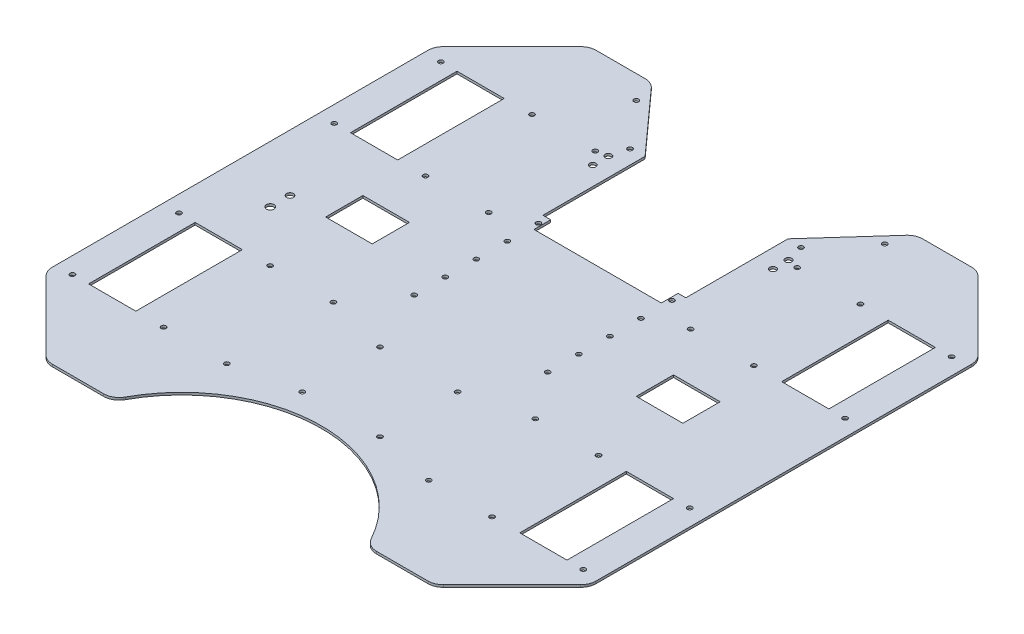
SolidWorks part; units mm, degrees
material "PMMA"
ref_plane "前视基准面" through (0, 0, 0) normal (0, 0, 1) x (1, 0, 0)
ref_plane "上视基准面" through (0, 0, 0) normal (0, 1, 0) x (1, 0, 0)
ref_plane "右视基准面" through (0, 0, 0) normal (1, 0, 0) x (0, 0, -1)
other "Configuration Table"
sketch "草图1" plane through (0, 0, 0) normal (0, 1, 0) x (1, 0, 0)
  line L0 (-125, 175) -> (-175, 125)
  line L1 (125, -175) -> (81.7103, -175)
  line L2 (175, -125) -> (175, 125)
  line L3 (125, 175) -> (85, 175)
  line L4 (-175, -125) -> (-175, 125)
  line L5 (-85, 175) -> (-40, 125)
  line L7 (125, 175) -> (175, 125)
  line L8 (175, -125) -> (125, -175)
  line L9 (-125, -175) -> (-175, -125)
  line L10 (40, 125) -> (85, 175)
  line L11 (-85, 175) -> (-125, 175)
  line L12 (40, 125) -> (40, 85)
  line L13 (40, 85) -> (-40, 85)
  line L14 (-40, 85) -> (-40, 125)
  line L15 (-153.994, 50) -> (-123.594, 50)
  line L16 (-123.594, 50) -> (-123.594, 118.58)
  line L17 (-123.594, 118.58) -> (-153.994, 118.58)
  line L18 (-153.994, 118.58) -> (-153.994, 50)
  line L19 (123.594, 50) -> (153.994, 50)
  line L20 (153.994, 50) -> (153.994, 118.58)
  line L21 (153.994, 118.58) -> (123.594, 118.58)
  line L22 (123.594, 118.58) -> (123.594, 50)
  line L23 (-175, 0) -> (175, 0) construction
  line L24 (-123.594, -118.58) -> (-153.994, -118.58)
  line L25 (-123.594, -50) -> (-123.594, -118.58)
  line L26 (-153.994, -50) -> (-123.594, -50)
  line L27 (-153.994, -118.58) -> (-153.994, -50)
  line L28 (153.994, -118.58) -> (123.594, -118.58)
  line L29 (153.994, -50) -> (153.994, -118.58)
  line L30 (123.594, -50) -> (153.994, -50)
  line L31 (123.594, -118.58) -> (123.594, -50)
  line L32 (-81.7103, -175) -> (-125, -175)
  line L33 (-80, 160) -> (-55, 131) construction
  line L34 (0, 85) -> (0, -124.4881) construction
  line L35 (-40, 85) -> (-40, -25)
  line L36 (-40, -25) -> (40, -25)
  line L37 (40, -25) -> (40, 85)
  line L38 (-40, -25) -> (-40, 66.9577)
  line L39 (-40, 66.9577) -> (40, 66.9577)
  line L40 (40, 66.9577) -> (40, -25)
  circle A0 centre (-55, 131) radius 1.55
  circle A1 centre (-80, 160) radius 1.55
  circle A2 centre (55, 131) radius 1.55
  circle A3 centre (80, 160) radius 1.55
  circle A4 centre (-65, 118.58) radius 1.55
  circle A5 centre (-65, 50) radius 1.55
  circle A6 centre (-105.72, 50) radius 1.55
  circle A7 centre (-105.72, 118.58) radius 1.55
  circle A12 centre (-164.434, 118.58) radius 1.55
  circle A13 centre (-164.434, 50) radius 1.55
  circle A14 centre (-65, -118.58) radius 1.55
  circle A15 centre (-65, -50) radius 1.55
  circle A16 centre (-105.72, -50) radius 1.55
  circle A17 centre (-105.72, -118.58) radius 1.55
  circle A18 centre (-164.434, -50) radius 1.55
  circle A19 centre (-164.434, -118.58) radius 1.55
  circle A20 centre (65, 50) radius 1.55
  circle A21 centre (105.72, 50) radius 1.55
  circle A22 centre (105.72, 118.58) radius 1.55
  circle A23 centre (65, 118.58) radius 1.55
  circle A24 centre (164.434, 118.58) radius 1.55
  circle A25 centre (164.434, 50) radius 1.55
  circle A26 centre (164.434, -118.58) radius 1.55
  circle A27 centre (164.434, -50) radius 1.55
  circle A28 centre (105.72, -50) radius 1.55
  circle A29 centre (105.72, -118.58) radius 1.55
  circle A30 centre (65, -118.58) radius 1.55
  circle A31 centre (65, -50) radius 1.55
  arc A32 (-81.7103, -175) -> (81.7103, -175) centre (0, -212.7283) cw
  circle A33 centre (25, -60) radius 1.55
  circle A34 centre (25, -110) radius 1.55
  circle A35 centre (-25, -60) radius 1.55
  circle A36 centre (-25, -110) radius 1.55
  circle A37 centre (-43, 120) radius 2.05
  circle A38 centre (-43, 110) radius 2.05
  circle A39 centre (-58, 110) radius 2.05
  circle A40 centre (-58, 120) radius 2.05
  circle A41 centre (43, 120) radius 2.05
  circle A42 centre (58, 120) radius 2.05
  circle A43 centre (58, 110) radius 2.05
  circle A44 centre (43, 110) radius 2.05
  circle A45 centre (43, -20) radius 1.55
  circle A46 centre (43, 0) radius 1.55
  circle A47 centre (43, 20) radius 1.55
  circle A48 centre (43, 40) radius 1.55
  circle A49 centre (43, 60) radius 1.55
  circle A50 centre (-43, -20) radius 1.55
  circle A51 centre (-43, 0) radius 1.55
  circle A52 centre (-43, 20) radius 1.55
  circle A53 centre (-43, 40) radius 1.55
  circle A54 centre (-43, 60) radius 1.55
  circle A55 centre (-138.4729, -4.4575) radius 2.205
  circle A56 centre (-138.4729, -17.1575) radius 2.5
  point P0 (0, 0)
  point P1 (-85, 175)
  point P2 (85, 175)
  point P3 (40, 125)
  point P4 (-40, 125)
  point P6 (125, 175)
  point P8 (175, 125)
  point P10 (175, -125)
  point P11 (125, -175)
  point P12 (-125, -175)
  point P13 (-175, -125)
  point P24 (-80, 160)
  point P25 (-55, 131)
  point P26 (55, 131)
  point P27 (80, 160)
  point P36 (-164.434, 118.58)
  point P37 (-164.434, 50)
  point P38 (-153.994, 118.58)
  point P39 (-123.594, 50)
  point P40 (-105.72, 118.58)
  point P41 (-105.72, 50)
  point P42 (-65, 118.58)
  point P43 (-65, 50)
  point P47 (-123.594, 118.58)
  point P53 (-153.994, 50)
  point P66 (-40, 85)
  point P67 (40, 85)
  point P70 (105.72, 50)
  point P71 (65, 50)
  point P72 (123.594, 50)
  point P73 (153.994, 50)
  point P74 (164.434, 50)
  point P75 (65, 118.58)
  point P76 (105.72, 118.58)
  point P77 (123.594, 118.58)
  point P78 (153.994, 118.58)
  point P81 (164.434, 118.58)
  point P85 (-65, -118.58)
  point P88 (-65, -50)
  point P91 (-105.72, -50)
  point P94 (-105.72, -118.58)
  point P101 (-164.434, -50)
  point P104 (-164.434, -118.58)
  point P118 (164.434, -118.58)
  point P121 (164.434, -50)
  point P128 (105.72, -50)
  point P131 (105.72, -118.58)
  point P134 (65, -118.58)
  point P137 (65, -50)
  point P157 (58, 110)
  point P158 (43, 110)
  point P159 (43, 120)
  point P160 (58, 120)
  point P189 (-43, 60)
  dimension "D29" = 3.1
  dimension "D30" = 3.1
  dimension "D31" = 3.1
  dimension "D32" = 3.1
  dimension "D40" = 3.1
  dimension "D41" = 3.1
  dimension "D42" = 3.1
  dimension "D43" = 3.1
  dimension "D44" = 3.1
  dimension "D45" = 3.1
  dimension "D46" = 3.1
  dimension "D47" = 3.1
  dimension "D48" = 3.1
  dimension "D49" = 3.1
  dimension "D60" = 3.1
  dimension "D61" = 3.1
  dimension "D62" = 43.2897
  dimension "D63" = 90
  dimension "D67" = 3.1
  dimension "D68" = 3.1
  dimension "D69" = 3.1
  dimension "D70" = 3.1
  dimension "D75" = 4.1
  dimension "D76" = 4.1
  dimension "D77" = 4.1
  dimension "D78" = 4.1
  dimension "D80" = 110
  dimension "D83" = 5
  dimension "D85" = 20
  dimension "D89" = 4.41
  dimension "D90" = 5
  dimension "D1" = 175
  dimension "D2" = 175
  dimension "D3" = 125
  dimension "D4" = 125
  dimension "D5" = 125
  dimension "D6" = 125
  dimension "D7" = 125
  dimension "D8" = 125
  dimension "D9" = 125
  dimension "D10" = 125
  dimension "D11" = 175
  dimension "D12" = 175
  dimension "D13" = 40
  dimension "D14" = 40
  dimension "D15" = 85
  dimension "D16" = 85
  dimension "D17" = 125
  dimension "D18" = 125
  dimension "D19" = 40
  dimension "D20" = 45
  dimension "D21" = 160
  dimension "D22" = 160
  dimension "D23" = 80
  dimension "D24" = 80
  dimension "D25" = 55
  dimension "D26" = 131
  dimension "D27" = 55
  dimension "D28" = 131
  dimension "D33" = 50
  dimension "D34" = 118.58
  dimension "D35" = 65
  dimension "D38" = 30.4
  dimension "D39" = 10.44
  dimension "D50" = 40
  dimension "D51" = 40
  dimension "D52" = 85
  dimension "D53" = 85
  dimension "D54" = 138.013
  dimension "D55" = 65
  dimension "D58" = 30.4
  dimension "D59" = 10.44
  dimension "D64" = 0
  dimension "D65" = 25
  dimension "D66" = 25
  dimension "D71" = 60
  dimension "D72" = 50
  dimension "D73" = 15
  dimension "D74" = 10
  dimension "D79" = 43
  dimension "D81" = 120
  dimension "D82" = 110
  dimension "D84" = 3
  dimension "D86" = 20
  dimension "D87" = 20
  dimension "D88" = 20
  dimension "D91" = 12.7
extrude "凸台-拉伸1" add sketch "草图1" along normal blind 1.5 contours A55 | A56 | A1 | A0 | L8 L1 A32 L32 L9 L4 L0 L11 L5 L14 L13 L12 L10 L3 L7 L2 | A5 | A3 | A2 | A4 | A7 | A12 | L16 L17 L18 L15 | A6 | L21 L22 L19 L20 | A13 | A16 | A17 | A14 | A15 | A18 | A19 | L25 L24 L27 L26 | A20 | A21 | A22 | A23 | A24 | A25 | A28 | A26 | A27 | L28 L31 L30 L29 | A30 | A31 | A29 | A35 | A36 | A33 | A34 | A39 | A40 | A37 | A38 | A43 | A42 | A41 | A44 region at (-138.4729, 0, 4.4575) region at (-138.4729, 0, 17.1575)
fillet "圆角1" radius 10 1 edges at (-40, 0.75, -125)
fillet "圆角2" radius 10 1 edges at (40, 0.75, -125)
fillet "圆角3" radius 10 12 edges at (-85, 0.75, -175) (85, 0.75, -175) (125, 0.75, -175) (175, 0.75, -125) (175, 0.75, 125) (125, 0.75, 175) (81.7103, 0.75, 175) (-81.7103, 0.75, 175) (-125, 0.75, 175) (-175, 0.75, 125) (-175, 0.75, -125) (-125, 0.75, -175)
sketch "草图2" plane through (0, 1.5, 0) normal (0, 1, 0) x (1, 0, 0)
  line L1 (-40, 85) -> (40, 85)
  line L2 (-40, 85) -> (-40, 55.3716)
  line L3 (-40, 55.3716) -> (40, 55.3716)
  line L4 (40, 85) -> (40, 55.3716)
extrude "切除-拉伸1" cut sketch "草图2" against normal blind 10
sketch "草图3" plane through (0, 1.5, 0) normal (0, 1, 0) x (1, 0, 0)
  line L0 (-87.875, -175) -> (-120.8579, -175) construction
  line L1 (-115, 19) -> (-85, 19)
  line L2 (-115, 19) -> (-115, -5)
  line L3 (-115, -5) -> (-85, -5)
  line L4 (-85, 19) -> (-85, -5)
  line L5 (-175, -120.8579) -> (-175, 120.8579) construction
  line L6 (120.8579, -175) -> (87.875, -175) construction
  line L7 (85, 19) -> (115, 19)
  line L8 (85, 19) -> (85, -5)
  line L9 (85, -5) -> (115, -5)
  line L10 (115, 19) -> (115, -5)
  line L11 (175, -120.8579) -> (175, 120.8579) construction
  dimension "D1" = 30
  dimension "D2" = 24
  dimension "D3" = 170
  dimension "D4" = 60
  dimension "D5" = 30
  dimension "D6" = 24
  dimension "D7" = 170
  dimension "D8" = 60
extrude "切除-拉伸2" cut sketch "草图3" against normal blind 10
extrude "切除-拉伸3" cut sketch "草图1<4>" along normal blind 10 contours A54 | A53 | A52 | A51 | A50 | A49 | A48 | A47 | A46 | A45
sketch "草图1<4>" plane through (0, 0, 0) normal (0, 1, 0) x (1, 0, 0) same geometry as "草图1"
sketch "草图5" plane through (0, 0, 0) normal (0, -1, 0) x (1, 0, 0)
  line L0 (-40, -55.3716) -> (-40, -121.1626) construction
  line L1 (-46, -65.9277) -> (46, -65.9277)
  line L2 (-46, -65.9277) -> (-46, -134.4558)
  line L3 (-46, -134.4558) -> (46, -134.4558)
  line L4 (46, -65.9277) -> (46, -134.4558)
  line L5 (40, -121.1626) -> (40, -55.3716) construction
  dimension "D1" = 6
  dimension "D2" = 6
extrude "切除-拉伸4" cut sketch "草图5" against normal blind 4
sketch "草图6" plane through (0, 1.5, 0) normal (0, 1, 0) x (1, 0, 0)
  line L0 (-40, 65.9277) -> (-46, 65.9277) construction
  line L1 (-41, 65.9277) -> (41, 65.9277)
  line L2 (-41, 65.9277) -> (-41, 55.1146)
  line L3 (-41, 55.1146) -> (41, 55.1146)
  line L4 (41, 65.9277) -> (41, 55.1146)
  line L5 (-40, 55.3716) -> (-40, 65.9277) construction
  line L6 (40, 65.9277) -> (40, 55.3716) construction
  dimension "D1" = 1
  dimension "D2" = 1
extrude "切除-拉伸5" cut sketch "草图6" against normal blind 10
